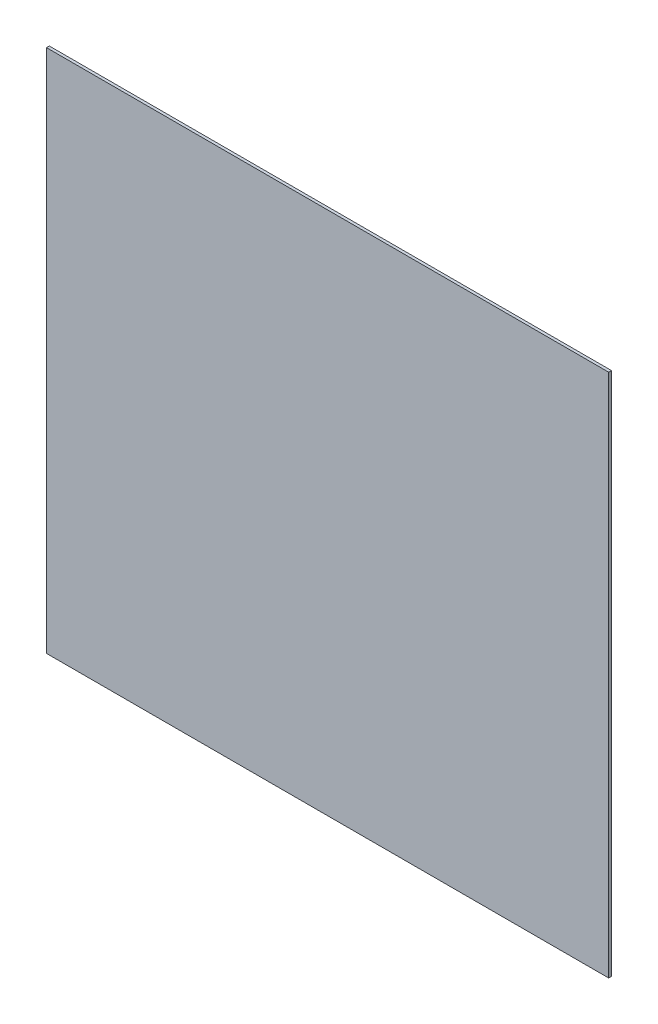
SolidWorks part; units mm, degrees
material "AISI 4130 Steel, normalized at 870C"
ref_plane "Front Plane" through (0, 0, 0) normal (0, 0, 1) x (1, 0, 0)
ref_plane "Top Plane" through (0, 0, 0) normal (0, 1, 0) x (1, 0, 0)
ref_plane "Right Plane" through (0, 0, 0) normal (1, 0, 0) x (0, 0, -1)
sketch "Sketch2" plane through (0, 0, 0) normal (0, 0, 1) x (1, 0, 0)
  line L1 (-150, 140) -> (150, 140)
  line L2 (-150, 140) -> (-150, -140)
  line L3 (-150, -140) -> (150, -140)
  line L4 (150, 140) -> (150, -140)
  dimension "D1" = 300
  dimension "D2" = 280
  dimension "D3" = 140
  dimension "D4" = 150
extrude "Boss-Extrude2" add sketch "Sketch2" along normal blind 1.5
